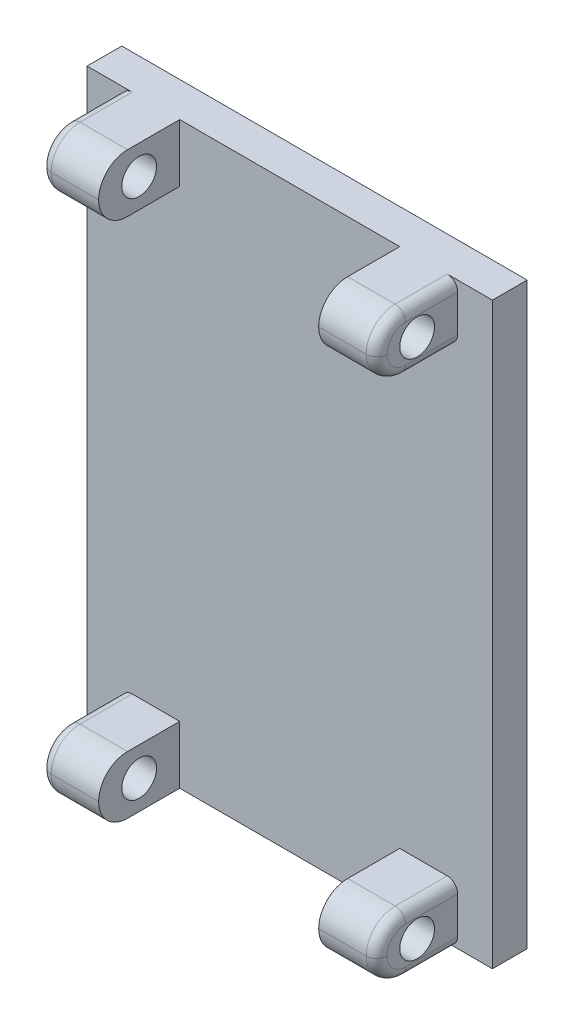
SolidWorks part; units mm, degrees
ref_plane "Front Plane" through (0, 0, 0) normal (0, 0, 1) x (1, 0, 0)
ref_plane "Top Plane" through (0, 0, 0) normal (0, 1, 0) x (1, 0, 0)
ref_plane "Right Plane" through (0, 0, 0) normal (1, 0, 0) x (0, 0, -1)
sketch "Sketch1" plane through (0, 0, 0) normal (0, 0, 1) x (1, 0, 0)
  line L1 (-17.5, -25) -> (17.5, -25)
  line L2 (-17.5, -25) -> (-17.5, 25)
  line L3 (-17.5, 25) -> (17.5, 25)
  line L4 (17.5, -25) -> (17.5, 25)
  line L5 (-17.5, -25) -> (17.5, 25) construction
  line L6 (-17.5, 25) -> (17.5, -25) construction
  point P0 (0, 0)
  dimension "D1" = 35
  dimension "D2" = 50
extrude "Boss-Extrude1" add sketch "Sketch1" along normal blind 3
sketch "Sketch2" plane through (0, 0, 3) normal (0, 0, 1) x (1, 0, 0)
  line L18 (-14.5, 25) -> (-9.5, 25)
  line L19 (-14.5, 25) -> (-14.5, 20)
  line L20 (-9.5, 25) -> (-9.5, 20)
  line L21 (-14.5, 20) -> (-9.5, 20)
  line L22 (17.5, 25) -> (-17.5, 25) construction
  line L23 (9.5, 25) -> (14.5, 25)
  line L24 (9.5, 25) -> (9.5, 20)
  line L25 (14.5, 25) -> (14.5, 20)
  line L26 (9.5, 20) -> (14.5, 20)
  line L27 (-9.5, -25) -> (-14.5, -25)
  line L28 (-9.5, -25) -> (-9.5, -20)
  line L29 (-14.5, -25) -> (-14.5, -20)
  line L30 (-9.5, -20) -> (-14.5, -20)
  line L31 (-17.5, -25) -> (17.5, -25) construction
  line L32 (9.5, -25) -> (14.5, -25)
  line L33 (9.5, -25) -> (9.5, -20)
  line L34 (14.5, -25) -> (14.5, -20)
  line L35 (9.5, -20) -> (14.5, -20)
  line L36 (-17.5, 25) -> (-17.5, -25) construction
  line L37 (17.5, -25) -> (17.5, 25) construction
  dimension "D1" = 5
  dimension "D2" = 3
  dimension "D3" = 3
  dimension "D4" = 3
  dimension "D5" = 3
  dimension "D6" = 5
extrude "Boss-Extrude2" add sketch "Sketch2" along normal blind 7
sketch "Sketch3" plane through (-14.5, 0, 0) normal (-1, 0, 0) x (0, 0, 1)
  line L0 (3, 25) -> (10, 20)
  line L1 (3, -20) -> (10, -25)
  circle A0 centre (6.5, 22.5) radius 1.5
  circle A1 centre (6.5, -22.5) radius 1.5
  dimension "D1" = 3
  dimension "D2" = 3
extrude "Cut-Extrude1" cut sketch "Sketch3" against normal up to surface (29 mm away) contours L0 A0 | L0 A0 | L1 A1 | L1 A1 region at (-14.5, 23.018, 6.87) region at (-14.5, 21.982, 6.13) region at (-14.5, -21.982, 6.87) region at (-14.5, -23.018, 6.13) up to face at (14.5, 22.5, 6.5)
fillet "Fillet1" radius 2.5 8 edges at (12, -25, 10) (12, -20, 10) (-12, -25, 10) (-12, -20, 10) (12, 20, 10) (12, 25, 10) (-12, 20, 10) (-12, 25, 10)
fillet "Fillet2" radius 0.9 16 edges at (14.5, -20, 5.25) (14.5, -25, 5.25) (14.5, -24.2678, 9.2678) (-14.5, -25, 5.25) (-14.5, -24.2678, 9.2678) (-14.5, -20, 5.25) (14.5, 25, 5.25) (14.5, 20, 5.25) (14.5, 20.7322, 9.2678) (-14.5, 20, 5.25) (-14.5, 20.7322, 9.2678) (-14.5, 25, 5.25) (14.5, -20.7322, 9.2678) (-14.5, -20.7322, 9.2678) (14.5, 24.2678, 9.2678) (-14.5, 24.2678, 9.2678)
